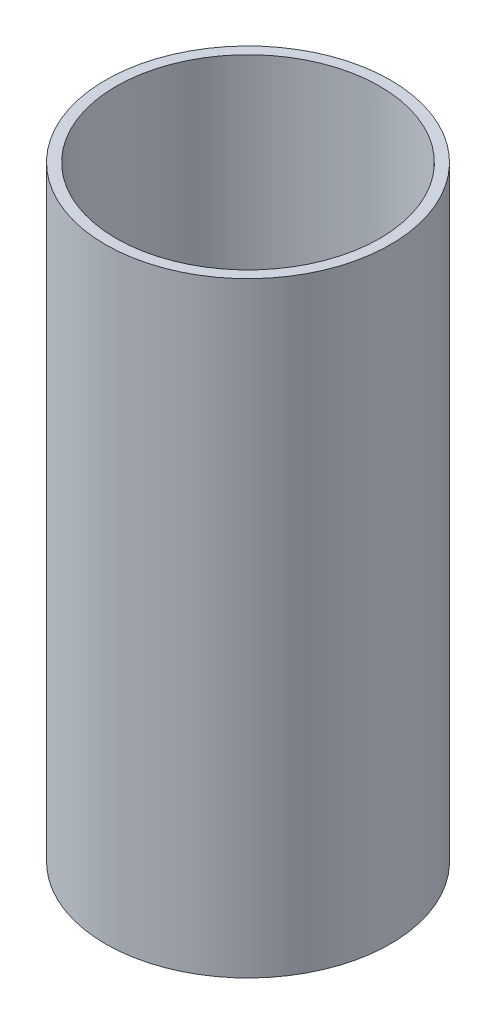
SolidWorks part; units mm, degrees
ref_plane "前视基准面" through (0, 0, 0) normal (0, 0, 1) x (1, 0, 0)
ref_plane "上视基准面" through (0, 0, 0) normal (0, 1, 0) x (1, 0, 0)
ref_plane "右视基准面" through (0, 0, 0) normal (1, 0, 0) x (0, 0, -1)
sketch "草图1" plane through (0, 0, 0) normal (0, 1, 0) x (1, 0, 0)
  circle A0 centre (0, 0) radius 4.7
  circle A1 centre (0, 0) radius 20
extrude "凸台-拉伸1" add sketch "草图1" along normal blind 2.5
sketch "草图2" plane through (0, 2.5, 0) normal (0, 1, 0) x (1, 0, 0)
  line L0 (0, 0) -> (0, -6)
  line L1 (0, 0) -> (-24.9951, -0.4942)
  line L2 (0, -6) -> (-17.0041, -2.2544)
  line L3 (0, 0) -> (0, 6)
  line L4 (0, 6) -> (-17.0756, 1.5634)
  line L5 (0, 0) -> (-18.4964, -0.3657)
  line L6 (-18.4964, -0.3657) -> (-18.4974, -0.3131)
  line L7 (-18.4974, -0.3131) -> (-18.495, -0.4365)
  line L8 (6, 0) -> (1.5634, 17.0756)
  line L9 (-6, 0) -> (-2.2544, 17.0041)
  line L10 (-0.3657, 18.4964) -> (-0.3131, 18.4974)
  line L11 (0, -6) -> (17.0756, -1.5634)
  line L12 (0, 6) -> (17.0041, 2.2544)
  line L13 (18.4964, 0.3657) -> (18.4974, 0.3131)
  line L14 (-6, 0) -> (-1.5634, -17.0756)
  line L15 (6, 0) -> (2.2544, -17.0041)
  line L16 (0.3657, -18.4964) -> (0.3131, -18.4974)
  arc A0 (-17.0041, -2.2544) -> (-18.495, -0.4365) centre (-16.5954, -0.3989) cw
  arc A1 (-17.0756, 1.5634) -> (-18.4974, -0.3131) centre (-16.5978, -0.2755) ccw
  circle A2 centre (0, 0) radius 18.5
  arc A3 (1.5634, 17.0756) -> (-0.3131, 18.4974) centre (-0.2755, 16.5978) ccw
  arc A4 (-2.2544, 17.0041) -> (-0.4365, 18.495) centre (-0.3989, 16.5954) cw
  arc A5 (17.0756, -1.5634) -> (18.4974, 0.3131) centre (16.5978, 0.2755) ccw
  arc A6 (17.0041, 2.2544) -> (18.495, 0.4365) centre (16.5954, 0.3989) cw
  arc A7 (-1.5634, -17.0756) -> (0.3131, -18.4974) centre (0.2755, -16.5978) ccw
  arc A8 (2.2544, -17.0041) -> (0.4365, -18.495) centre (0.3989, -16.5954) cw
  point P43 (0, 0)
  dimension "D1" = 1.9
  dimension "D2" = 4
extrude "凸台-拉伸2" add sketch "草图2" along normal blind 2.5 contours L12 A6 A2 A3 L8 | A7 A2 A0 L7 L6 A1 L10 A3 L13 A5 L16 | L9 A4 A2 A1 L4 | A7 L14 L2 A0 A2 | L15 A8 A2 A5 L11 region at (-9.4133, 2.5, 9.8122) region at (9.8121, 2.5, 9.4133) region at (-0.1921, 2.5, -19.4334) region at (-9.8121, 2.5, -9.4133) region at (9.4133, 2.5, -9.8121)
fillet "圆角1" radius 5 4 edges at (-4.7107, 3.75, 4.9624) (-4.9624, 3.75, -4.7107) (4.9624, 3.75, 4.7107) (4.7107, 3.75, -4.9624)
sketch "草图3" plane through (0, 5, 0) normal (0, 1, 0) x (1, 0, 0)
  circle A0 centre (0, 0) radius 20
  circle A1 centre (0, 0) radius 18.5001
extrude "凸台-拉伸3" add sketch "草图3" along normal blind 80
